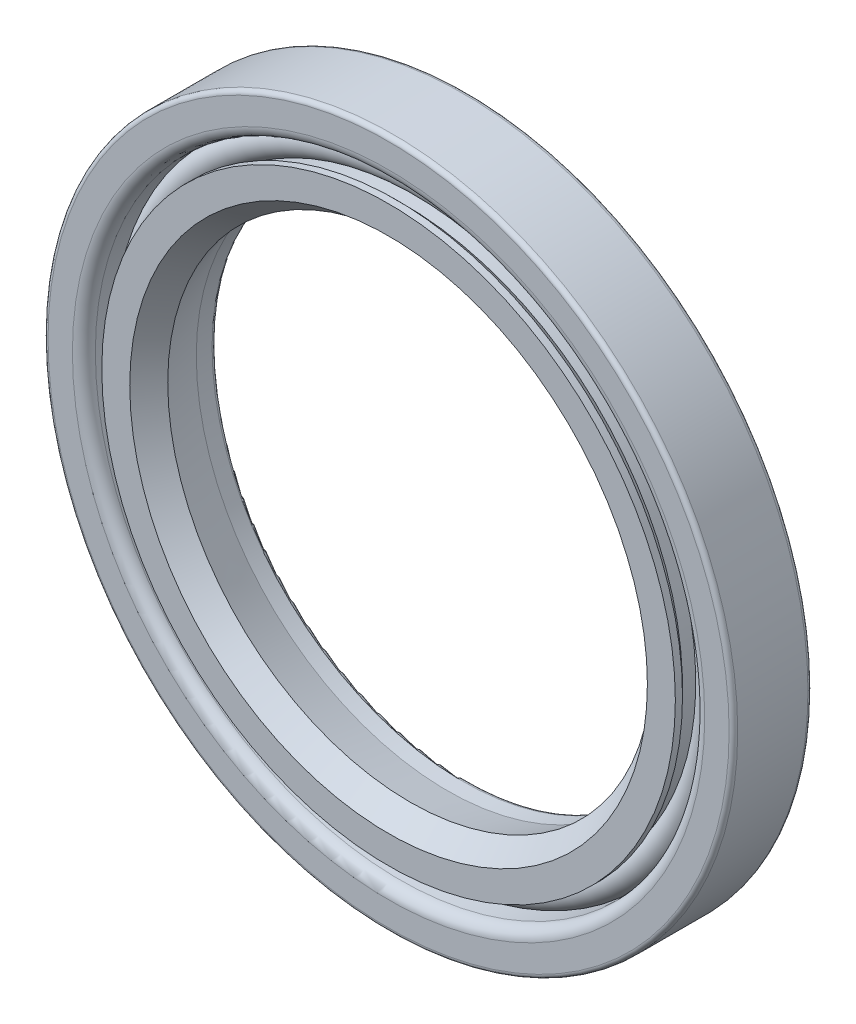
SolidWorks part; units mm, degrees
ref_plane "Front Plane" through (0, 0, 0) normal (0, 0, 1) x (1, 0, 0)
ref_plane "Top Plane" through (0, 0, 0) normal (0, 1, 0) x (1, 0, 0)
ref_plane "Right Plane" through (0, 0, 0) normal (1, 0, 0) x (0, 0, -1)
sketch "Sketch1" plane through (0, 0, 0) normal (1, 0, 0) x (0, 0, -1)
  line L0 (0, 0) -> (-8.7293, 0) construction
  line L1 (0, 17.81) -> (0, 23.75)
  line L2 (-0.3, 17.51) -> (-1.4, 17.51)
  line L3 (-0.3, 24.05) -> (-5.2, 24.05)
  line L4 (-5.5, 23.75) -> (-5.5, 22.05)
  line L5 (-4.7, 21.25) -> (-3.3, 21.25)
  line L6 (-2.5, 20.45) -> (-2.5, 20.25)
  line L7 (-3.3, 19.45) -> (-4.45, 19.45)
  line L8 (-1.4, 17.51) -> (-4, 16.9)
  line L9 (-4, 16.9) -> (-5.5, 18.05)
  line L10 (-5.5, 18.05) -> (-5.5, 20)
  line L12 (-5.5, 20) -> (-5, 20)
  line L13 (-5, 20) -> (-4.45, 19.45)
  arc A1 (-5.5, 22.05) -> (-4.7, 21.25) centre (-4.7, 22.05) ccw
  arc A2 (-3.3, 21.25) -> (-2.5, 20.45) centre (-3.3, 20.45) cw
  arc A3 (-2.5, 20.25) -> (-3.3, 19.45) centre (-3.3, 20.25) cw
  arc A4 (0, 17.81) -> (-0.3, 17.51) centre (-0.3, 17.81) cw
  arc A5 (0, 23.75) -> (-0.3, 24.05) centre (-0.3, 23.75) ccw
  arc A6 (-5.2, 24.05) -> (-5.5, 23.75) centre (-5.2, 23.75) ccw
  dimension "D2" = 1.4
  dimension "D8" = 0.8
  dimension "D9" = 0.3
  dimension "D1" = 5.5
  dimension "D3" = 3
  dimension "D4" = 38.9
  dimension "D5" = 42.5
  dimension "D6" = 48.1
  dimension "D7" = 35.02
  dimension "D10" = 33.8
  dimension "D11" = 36.1
  dimension "D12" = 1.5
  dimension "D13" = 0.5
  dimension "D14" = 45
  dimension "D15" = 40
revolve "Revolve1" add sketch "Sketch1" angle 360 about L0
ref_axis "Axis1" through (0, 0, 5.2) along (0, 0, -1)
sketch "Sketch2" plane through (0, 0, 0) normal (1, 0, 0) x (0, 0, -1)
  line L0 (0, 0) -> (-14.8701, 0) construction
  line L1 (-5.2, 0) -> (-0.3, 0) construction
  line L2 (0, -23.75) -> (0, 23.75) construction
  circle A0 centre (-3, 20.3388) radius 1
  dimension "D2" = 3
  dimension "D3" = 2
  dimension "D1" = 40.6777
revolve "Revolve2" add sketch "Sketch2" angle 360 about L0
sketch "Sketch3" plane through (0, 0, 0) normal (1, 0, 0) x (0, 0, -1)
  line L0 (0, 0) -> (-12.1608, 0) construction
  line L1 (-4.5, 23.05) -> (-1.4, 23.05)
  line L2 (-0.6, 22.25) -> (-0.6, 19.45)
  line L3 (-0.6, 19.45) -> (-0.9, 19.45)
  line L4 (-0.9, 19.45) -> (-0.9, 22.25)
  line L5 (-1.4, 22.75) -> (-4.5, 22.75)
  line L6 (-4.5, 23.05) -> (-4.5, 22.75)
  line L7 (0, -23.75) -> (0, 23.75) construction
  line L8 (-0.3, 24.05) -> (-5.2, 24.05) construction
  line L9 (-5.5, 23.75) -> (-5.5, 22.05) construction
  arc A0 (-0.9, 22.25) -> (-1.4, 22.75) centre (-1.4, 22.25) ccw
  arc A1 (-1.4, 23.05) -> (-0.6, 22.25) centre (-1.4, 22.25) cw
  point P15 (-0.6, 20.85)
  point P18 (-4.5, 22.9)
  dimension "D1" = 0.5
  dimension "D2" = 0.8
  dimension "D3" = 0.3
  dimension "D4" = 0.3
  dimension "D5" = 0.6
  dimension "D6" = 1
  dimension "D7" = 1
  dimension "D8" = 3.6
revolve "Revolve4" add sketch "Sketch3" angle 360 about L0
